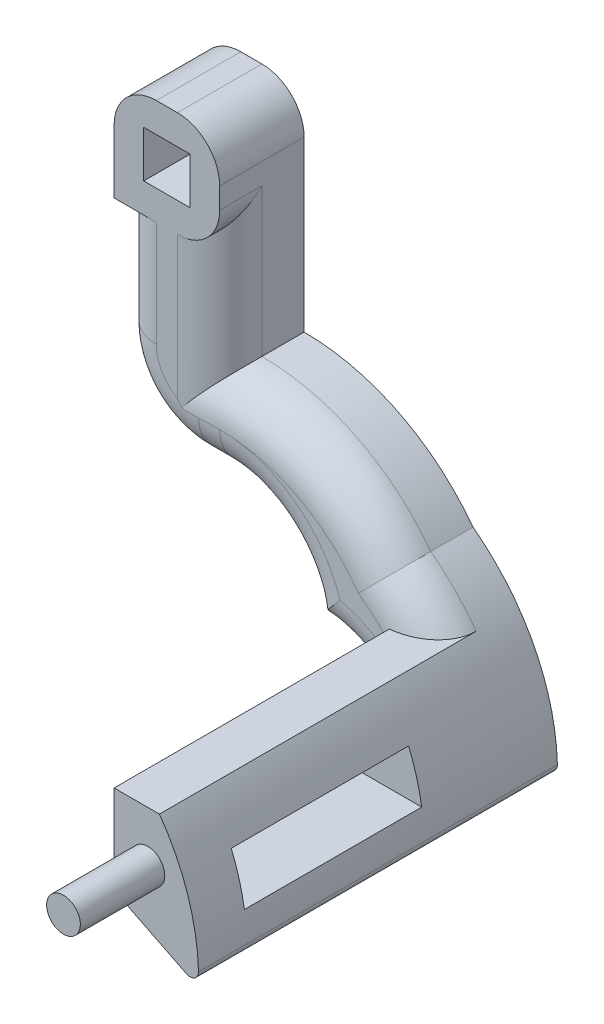
SolidWorks part; units mm, degrees
ref_plane "Front Plane" through (0, 0, 0) normal (0, 0, 1) x (1, 0, 0)
ref_plane "Top Plane" through (0, 0, 0) normal (0, 1, 0) x (1, 0, 0)
ref_plane "Right Plane" through (0, 0, 0) normal (1, 0, 0) x (0, 0, -1)
sketch "Sketch1" plane through (0, 0, 0) normal (0, 1, 0) x (1, 0, 0)
  line L1 (0, 0) -> (36.83, 0)
  line L2 (0, 0) -> (0, 16.51)
  line L3 (0, 16.51) -> (36.83, 16.51)
  line L4 (36.83, 0) -> (36.83, 16.51)
  dimension "D1" = 36.83
  dimension "D2" = 16.51
extrude "Boss-Extrude1" add sketch "Sketch1" along normal blind 6.35
hole_wizard "Ø3.0mm Dowel Hole1" positions "Sketch5" profile "Sketch4" hole size "Ø3.0" standard "ISO" end condition through all
sketch "Sketch5" plane through (0, 6.35, 0) normal (0, 1, 0) x (1, 0, 0)
  line L0 (0, 0) -> (36.83, 0) construction
  line L1 (0, 16.51) -> (0, 0) construction
  point P0 (5.08, 8.255)
  point P2 (12.7, 8.255)
  dimension "D1" = 8.255
  dimension "D2" = 5.08
  dimension "D3" = 7.62
sketch "Sketch4" plane through (5.08, 6.35, -8.255) normal (1, 0, 0) x (0, 0, 1)
  line L0 (0, 0) -> (0, 6.35)
  line L1 (0, 6.35) -> (1.5, 6.35)
  line L2 (1.5, 6.35) -> (1.5, 0)
  line L5 (1.5, 0) -> (0, 0)
  line L11 (0, -6.35) -> (0, 107.95) construction
  dimension "Thru Hole Dia." = 3
  dimension "Thru Hole Depth" = 6.35
chamfer "Chamfer1" distance 0.254 angle 45 4 edges at (12.7, 6.35, -6.755) (5.08, 6.35, -6.755) (5.08, 0, -6.755) (12.7, 0, -6.755)
fillet "Fillet2" radius 3.81 2 edges at (0, 3.175, 0) (0, 3.175, -16.51)
sketch "Sketch14" plane through (0, 0, 0) normal (0, 0, 1) x (1, 0, 0)
  line L1 (36.83, 6.35) -> (30.48, 6.35)
  line L2 (36.83, 6.35) -> (36.83, -11.43)
  line L3 (36.83, -11.43) -> (30.48, -11.43)
  line L4 (30.48, 6.35) -> (30.48, -11.43)
  dimension "D1" = 6.35
  dimension "D2" = 17.78
extrude "Boss-Extrude8" add sketch "Sketch14" along normal blind 5.08
sketch "Sketch15" plane through (0, 0, -16.51) normal (0, 0, -1) x (-1, 0, 0)
  line L1 (-36.83, 6.35) -> (-30.48, 6.35)
  line L2 (-36.83, 6.35) -> (-36.83, -11.43)
  line L3 (-36.83, -11.43) -> (-30.48, -11.43)
  line L4 (-30.48, 6.35) -> (-30.48, -11.43)
  dimension "D1" = 17.78
  dimension "D2" = 6.35
extrude "Boss-Extrude9" add sketch "Sketch15" along normal blind 5.08
sketch "Sketch16" plane through (36.83, 0, 0) normal (1, 0, 0) x (0, 0, -1)
  line L0 (0, -11.43) -> (0, 0) construction
  line L1 (-5.08, -11.43) -> (0, -11.43)
  line L2 (-5.08, -11.43) -> (-5.08, -6.35)
  line L3 (-5.08, -6.35) -> (0, -6.35)
  line L4 (0, -11.43) -> (0, -6.35)
  line L5 (21.59, 6.35) -> (21.59, -11.43) construction
  line L6 (16.51, -11.43) -> (21.59, -11.43)
  line L7 (16.51, -11.43) -> (16.51, -6.35)
  line L8 (16.51, -6.35) -> (21.59, -6.35)
  line L9 (21.59, -11.43) -> (21.59, -6.35)
  dimension "D1" = 5.08
  dimension "D2" = 5.08
extrude "Boss-Extrude10" add sketch "Sketch16" along normal blind 10.16
sketch "Sketch18" plane through (0, -11.43, 0) normal (0, -1, 0) x (1, 0, 0)
  line L0 (30.48, 0) -> (46.99, 0) construction
  line L1 (46.99, 5.08) -> (41.91, 5.08)
  line L2 (46.99, 5.08) -> (46.99, 0)
  line L3 (46.99, 0) -> (41.91, 0)
  line L4 (41.91, 5.08) -> (41.91, 0)
  line L5 (46.99, -21.59) -> (30.48, -21.59) construction
  line L6 (46.99, -16.51) -> (41.91, -16.51)
  line L7 (46.99, -16.51) -> (46.99, -21.59)
  line L8 (46.99, -21.59) -> (41.91, -21.59)
  line L9 (41.91, -16.51) -> (41.91, -21.59)
  dimension "D1" = 5.08
  dimension "D2" = 5.08
extrude "Boss-Extrude12" add sketch "Sketch18" along normal blind 5.08
sketch "Sketch19" plane through (46.99, 0, 0) normal (1, 0, 0) x (0, 0, -1)
  line L0 (0, -16.51) -> (0, -6.35) construction
  line L1 (-5.08, -16.51) -> (0, -16.51)
  line L2 (-5.08, -16.51) -> (-5.08, -11.43)
  line L3 (-5.08, -11.43) -> (0, -11.43)
  line L4 (0, -16.51) -> (0, -11.43)
  line L5 (21.59, -16.51) -> (21.59, -6.35) construction
  line L6 (16.51, -16.51) -> (21.59, -16.51)
  line L7 (16.51, -16.51) -> (16.51, -11.43)
  line L8 (16.51, -11.43) -> (21.59, -11.43)
  line L9 (21.59, -16.51) -> (21.59, -11.43)
extrude "Boss-Extrude13" add sketch "Sketch19" along normal blind 5.08
sketch "Sketch20" plane through (0, -16.51, 0) normal (0, -1, 0) x (1, 0, 0)
  line L0 (41.91, 0) -> (52.07, 0) construction
  line L1 (52.07, 5.08) -> (46.99, 5.08)
  line L2 (52.07, 5.08) -> (52.07, 0)
  line L3 (52.07, 0) -> (46.99, 0)
  line L4 (46.99, 5.08) -> (46.99, 0)
  line L5 (41.91, -21.59) -> (52.07, -21.59) construction
  line L6 (52.07, -16.51) -> (46.99, -16.51)
  line L7 (52.07, -16.51) -> (52.07, -21.59)
  line L8 (52.07, -21.59) -> (46.99, -21.59)
  line L9 (46.99, -16.51) -> (46.99, -21.59)
extrude "Boss-Extrude14" add sketch "Sketch20" along normal blind 5.588
sketch "Sketch21" plane through (0, 0, -21.59) normal (0, 0, -1) x (-1, 0, 0)
  line L0 (-46.99, -22.098) -> (-52.07, -22.098)
  line L1 (-52.07, -22.098) -> (-46.99, -19.558)
  line L2 (-46.99, -22.098) -> (-46.99, -16.51) construction
  line L3 (-46.99, -19.558) -> (-46.99, -22.098)
  dimension "D1" = 2.54
extrude "Cut-Extrude5" cut sketch "Sketch21" against normal through all
sketch "Sketch22" plane through (0, 0, -16.51) normal (0, 0, 1) x (1, 0, 0)
  line L0 (52.07, -22.098) -> (46.99, -19.558)
  line L1 (46.99, -19.558) -> (46.99, -14.224)
  line L2 (46.99, -14.224) -> (52.07, -14.224)
  line L3 (52.07, -11.43) -> (52.07, -22.098) construction
  line L4 (52.07, -14.224) -> (52.07, -22.098)
  dimension "D1" = 7.874
extrude "Boss-Extrude15" add sketch "Sketch22" along normal blind 16.51
sketch "Sketch23" plane through (46.99, 0, 0) normal (-1, 0, 0) x (0, 0, 1)
  line L0 (5.08, -19.558) -> (-21.59, -19.558) construction
  line L1 (-13.589, -19.558) -> (-2.921, -19.558)
  line L2 (-13.589, -19.558) -> (-13.589, -16.764)
  line L3 (-13.589, -16.764) -> (-2.921, -16.764)
  line L4 (-2.921, -19.558) -> (-2.921, -16.764)
  line L6 (0, -14.224) -> (-16.51, -14.224) construction
  point P6 (-8.255, -14.224)
  dimension "D1" = 2.794
  dimension "D2" = 10.668
  dimension "D3" = 5.334
extrude "Cut-Extrude6" cut sketch "Sketch23" against normal blind 16.51
fillet "Fillet3" radius 12.7 3 edges at (52.07, -11.43, -19.05) (46.99, -6.35, -19.05) (46.99, -6.35, 2.54)
fillet "Fillet4" radius 5.08 6 edges at (30.48, -11.43, -19.05) (30.48, -11.43, 2.54)
fillet "Fillet5" radius 0.508 1 edges
fillet "Fillet6" radius 2.54 20 edges at (40.4221, -12.9179, -16.51) (31.9679, -9.9421, -16.51) (40.4221, -12.9179, 0) (31.9679, -9.9421, 0) (30.48, 6.35, 2.54) (30.48, 6.35, -19.05) (36.83, 0, -8.255) (36.83, 6.35, -8.255) (48.4608, -12.7217, -16.51) (42.5096, -7.6908, -16.51) (48.4608, -12.7217, 0) (45.1165, -17.3398, 0) (45.1165, -17.3398, -16.51) (30.48, -3.175, -16.51) (30.48, -3.175, 0) (36.83, -3.175, -16.51)
sketch "Sketch24" plane through (0, 0, 0) normal (0, 0, 1) x (1, 0, 0)
  line L1 (0, 8.5066) -> (56.668, 8.5066)
  line L2 (0, 8.5066) -> (0, -31.5744)
  line L3 (0, -31.5744) -> (56.668, -31.5744)
  line L4 (56.668, 8.5066) -> (56.668, -31.5744)
extrude "Cut-Extrude7" cut sketch "Sketch24" along normal through all
sketch "Sketch26" plane through (0, 0, -16.51) normal (0, 0, -1) x (-1, 0, 0)
  line L1 (0, 0) -> (-38.8756, 0)
  line L2 (0, 0) -> (0, 22.8216)
  line L3 (0, 22.8216) -> (-38.8756, 22.8216)
  line L4 (-38.8756, 0) -> (-38.8756, 22.8216)
extrude "Cut-Extrude9" cut sketch "Sketch26" against normal through all
sketch "Sketch27" plane through (0, 0, -21.59) normal (0, 0, -1) x (-1, 0, 0)
  line L0 (-36.83, 3.81) -> (-36.83, -6.35) construction
  line L1 (-35.052, 4.572) -> (-32.258, 4.572)
  line L2 (-35.052, 4.572) -> (-35.052, 1.778)
  line L3 (-35.052, 1.778) -> (-32.258, 1.778)
  line L4 (-32.258, 4.572) -> (-32.258, 1.778)
  line L5 (-33.02, 6.35) -> (-34.29, 6.35) construction
  dimension "D1" = 1.778
  dimension "D2" = 2.794
  dimension "D3" = 1.778
  dimension "D4" = 2.794
extrude "Cut-Extrude10" cut sketch "Sketch27" against normal blind 5.08
sketch "Sketch29" plane through (0, 0, 0) normal (0, 0, 1) x (1, 0, 0)
  line L0 (49.7156, -14.224) -> (46.99, -14.224) construction
  line L1 (46.99, -14.224) -> (46.99, -19.558) construction
  circle A0 centre (49.022, -17.272) radius 1.016
  dimension "D1" = 2.032
  dimension "D2" = 3.048
  dimension "D3" = 2.032
extrude "Boss-Extrude16" add sketch "Sketch29" along normal blind 5.08
